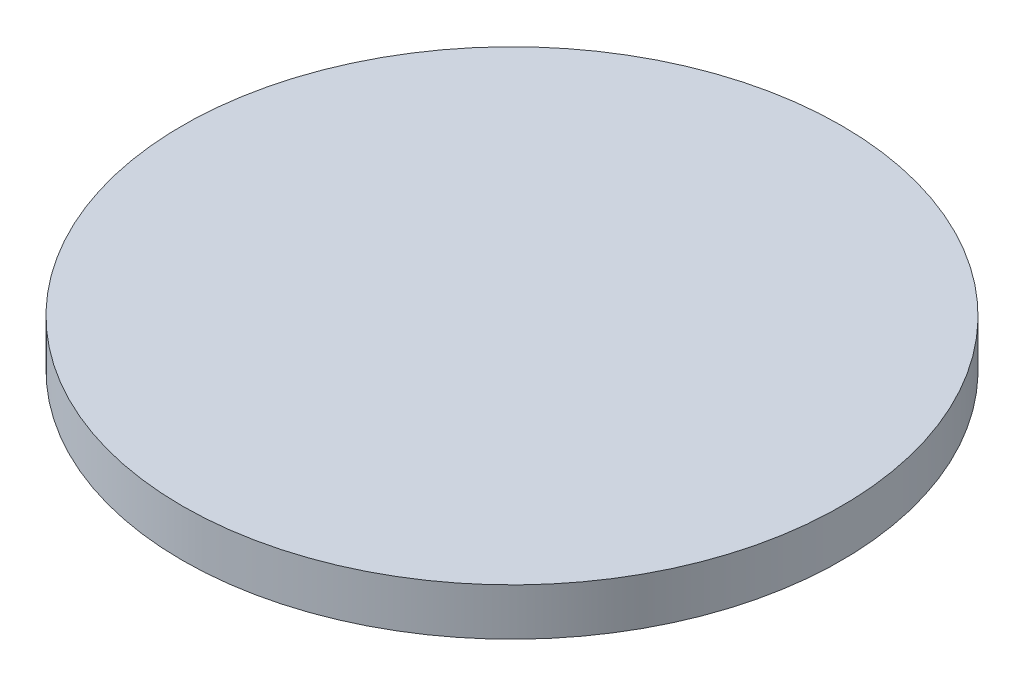
SolidWorks part; units mm, degrees
ref_plane "Front Plane" through (0, 0, 0) normal (0, 0, 1) x (1, 0, 0)
ref_plane "Top Plane" through (0, 0, 0) normal (0, 1, 0) x (1, 0, 0)
ref_plane "Right Plane" through (0, 0, 0) normal (1, 0, 0) x (0, 0, -1)
sketch "Sketch1" plane through (0, 0, 0) normal (0, 1, 0) x (1, 0, 0)
  circle A0 centre (0, 0) radius 70
  dimension "D1" = 140
extrude "Boss-Extrude1" add sketch "Sketch1" along normal blind 10
sketch "Sketch2" plane through (0, 0, 0) normal (0, -1, 0) x (1, 0, 0)
  circle A2 centre (0, 0) radius 65
  circle A3 centre (0, 0) radius 65
  dimension "D1" = 5
extrude "Boss-Extrude2" add sketch "Sketch2" along normal blind 3
